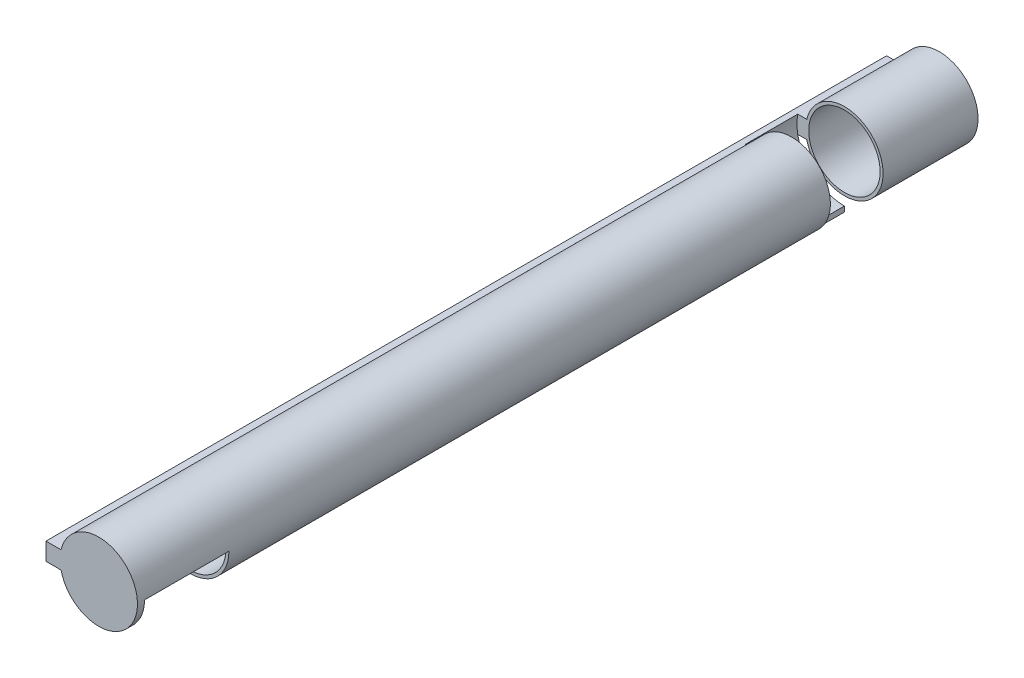
SolidWorks part; units mm, degrees
material "Manual Density from Real Component Plastica Fusoliera"
ref_plane "Piano frontale" through (0, 0, 0) normal (0, 0, 1) x (1, 0, 0)
ref_plane "Piano superiore" through (0, 0, 0) normal (0, 1, 0) x (1, 0, 0)
ref_plane "Piano destro" through (0, 0, 0) normal (1, 0, 0) x (0, 0, -1)
sketch "Schizzo1" plane through (0, 0, 0) normal (0, 0, 1) x (1, 0, 0)
  circle A0 centre (0, 0) radius 11
  circle A1 centre (0, 0) radius 10.15
  dimension "D1" = 22
  dimension "D2" = 20.3
extrude "Tubo" add sketch "Schizzo1" along normal blind 210
sketch "Schizzo2" plane through (0, 0, 210) normal (0, 0, 1) x (1, 0, 0)
  line L0 (0, -10.15) -> (0, -11)
  line L1 (10.15, 0) -> (11, 0)
  arc A0 (11, 0) -> (0, -11) centre (0, 0) ccw
  arc A2 (0, -10.15) -> (10.15, 0) centre (0, 0) cw
  circle A4 centre (0, 0) radius 10.15 construction
  circle A5 centre (0, 0) radius 11 construction
extrude "IngressoCavi" add sketch "Schizzo2" along normal blind 27
sketch "Schizzo4" plane through (0, 0, 210) normal (0, 0, 1) x (1, 0, 0)
  circle A0 centre (0, 0) radius 11
  circle A1 centre (0, 0) radius 6.5
  dimension "D1" = 22
  dimension "D2" = 13
extrude "FondoCorsa" add sketch "Schizzo4" along normal blind 3
sketch "Schizzo5" plane through (0, 0, 237) normal (0, 0, 1) x (1, 0, 0)
  circle A0 centre (0, 0) radius 11
  arc A1 (11, 0) -> (0, -11) centre (0, 0) ccw construction
extrude "Tappo" add sketch "Schizzo5" along normal blind 2
sketch "Schizzo6" plane through (0, 0, 0) normal (0, 0, 1) x (1, 0, 0)
  line L0 (-11, 2.5) -> (-15, 2.5)
  line L1 (-11, 2.5) -> (-10.7121, 2.5)
  line L2 (-11, 2.5) -> (-11, -2.5) construction
  line L3 (-11, -2.5) -> (-10.7121, -2.5)
  line L4 (-10.7121, 2.5) -> (-10.7121, -2.5)
  line L5 (-15, 2.5) -> (-15, -2.5)
  line L6 (-15, -2.5) -> (-11, -2.5)
  circle A0 centre (0, 0) radius 11 construction
  point P8 (-11, 0)
  dimension "D1" = 5
  dimension "D2" = 4
extrude "BaseInferiore" add sketch "Schizzo6" along normal up to surface (239 mm away) up to face at (11, 0, 239)
ref_plane "PianoInizioAnello" through (0, 0, 27) normal (0, 0, 1) x (1, 0, 0)
sketch "Schizzo7" plane through (0, 0, 27) normal (0, 0, 1) x (1, 0, 0)
  circle A0 centre (0, 0) radius 13.5
  dimension "D1" = 27
extrude "TaglioAnello" cut sketch "Schizzo7" along normal blind 15
sketch "Schizzo8" plane through (0, 0, 27) normal (0, 0, 1) x (1, 0, 0)
  line L0 (-15, 2.5) -> (-15, -2.5) construction
  line L1 (-15, 0) -> (-13.5, 0)
  line L2 (0, -13.5) -> (0, -15)
  arc A1 (-13.5, 0) -> (0, -13.5) centre (0, 0) ccw
  arc A2 (-15, 0) -> (0, -15) centre (0, 0) ccw
  dimension "D1" = 13.5
extrude "SupportoAnello" add sketch "Schizzo8" along normal blind 15
sketch "Schizzo9" plane through (0, 0, 210) normal (0, 0, -1) x (-1, 0, 0)
  line L0 (-10.15, 0) -> (0, 0)
  line L1 (0, 0) -> (0, -10.15)
  arc A0 (-10.15, 0) -> (0, -10.15) centre (0, 0) ccw
  circle A1 centre (0, 0) radius 10.15 construction
extrude "FacilitazioneCavi" cut sketch "Schizzo9" against normal up to surface (3 mm away) up to face at (6.5, 0, 213)
fillet "RaccordoFacilitazioneCavi" radius 8 2 edges at (0, -6.5, 211.5) (6.5, 0, 211.5)
